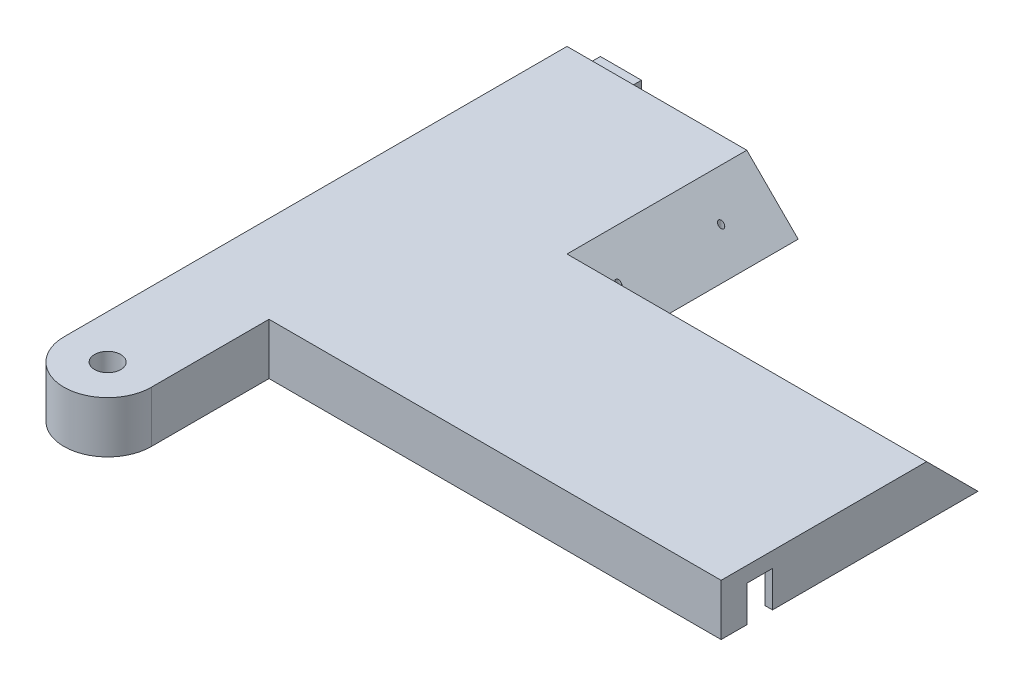
SolidWorks part; units mm, degrees
ref_plane "Front Plane" through (0, 0, 0) normal (0, 0, 1) x (1, 0, 0)
ref_plane "Top Plane" through (0, 0, 0) normal (0, 1, 0) x (1, 0, 0)
ref_plane "Right Plane" through (0, 0, 0) normal (1, 0, 0) x (0, 0, -1)
sketch "CornerrSketch1" plane through (0, 0, 0) normal (0, 1, 0) x (1, 0, 0)
  line L0 (0, 195.825) -> (90, 195.825)
  line L5 (90, 195.825) -> (90, 145.825)
  line L6 (90, 145.825) -> (210, 145.825)
  line L7 (210, 45.825) -> (210, 145.825)
  line L11 (34, 0) -> (34, 45.825)
  line L12 (34, 45.825) -> (210, 45.825)
  line L13 (0, 195.825) -> (0, 0)
  arc A0 (0, 0) -> (34, 0) centre (17, 0) ccw
  point P2 (45, 195.825)
  dimension "D3" = 34
  dimension "D4" = 90
  dimension "D2" = 100
  dimension "D1" = 45.825
  dimension "D6" = 210
  dimension "D5" = 150
extrude "CornerBoss-Extrude1" add sketch "CornerrSketch1" along normal blind 20
shell "Shell4" thickness 3 removed face at (83.5, 0, -94.7438)
sketch "PutPartialShellbackSketch1" plane through (0, 17, 0) normal (0, -1, 0) x (1, 0, 0)
  line L0 (67, -122.825) -> (67, -192.825)
  line L1 (67, -192.825) -> (87, -192.825)
  line L2 (87, -192.825) -> (87, -142.825)
  line L3 (87, -142.825) -> (207, -142.825)
  line L4 (207, -142.825) -> (207, -122.825)
  line L5 (207, -122.825) -> (67, -122.825)
  line L10 (87, -192.825) -> (3, -192.825) construction
  line L11 (207, -48.825) -> (207, -142.825) construction
  line L12 (210, -145.825) -> (90, -145.825) construction
  line L13 (90, -145.825) -> (90, -195.825) construction
  dimension "D1" = 23
  dimension "D2" = 23
extrude "PutPartialShellBackBoss-Extrude1" add sketch "PutPartialShellbackSketch1" along normal blind 17
sketch "PadSketch2" plane through (0, 17, 0) normal (0, -1, 0) x (1, 0, 0)
  circle A0 centre (17, 0) radius 12
  dimension "D1" = 24
extrude "PadBoss-Extrude2" add sketch "PadSketch2" along normal blind 10
sketch "TabHoleCutsSketch1" plane through (0, 20, 0) normal (0, 1, 0) x (1, 0, 0)
  line L4 (210, 145.825) -> (90, 145.825) construction
  line L5 (210, 45.825) -> (210, 145.825) construction
  line L6 (90, 195.825) -> (0, 195.825) construction
  line L7 (90, 145.825) -> (90, 195.825) construction
  circle A0 centre (80, 175.825) radius 1
  circle A1 centre (80, 135.825) radius 1
  circle A2 centre (135, 135.825) radius 1
  circle A3 centre (190, 135.825) radius 1
  point P16 (90, 170.825)
  dimension "D6" = 2
  dimension "D3" = 55
  dimension "D5" = 10
  dimension "D1" = 20
  dimension "D4" = 20
  dimension "D2" = 10
extrude "TabHoleCutsCut-Extrude1" cut sketch "TabHoleCutsSketch1" against normal through all
sketch "StepperShaftHoleCutSketch3" plane through (0, 7, 0) normal (0, -1, 0) x (1, 0, 0)
  circle A0 centre (17, 0) radius 5.1
  dimension "D1" = 10.2
extrude "StepperShaftHoleCut-Extrude1" cut sketch "StepperShaftHoleCutSketch3" against normal through all
sketch "ThreadedNutMountHolesSketch4" plane through (0, 7, 0) normal (0, -1, 0) x (-1, 0, 0)
  circle A8 centre (-17, 8) radius 1
  circle A9 centre (-17, -8) radius 1
  circle A10 centre (-25, 0) radius 1
  circle A11 centre (-9, 0) radius 1
  dimension "D1" = 2
  dimension "D2" = 8
  dimension "D3" = 16
  dimension "D4" = 8
  dimension "D5" = 16
extrude "ThreadedNutMountHolesCut-Extrude2" cut sketch "ThreadedNutMountHolesSketch4" against normal blind 10
sketch "BRPegHoleSketch1" plane through (210, 0, 0) normal (1, 0, 0) x (0, 0, -1)
  line L1 (55.825, 14) -> (65.825, 14)
  line L2 (55.825, 14) -> (55.825, 0)
  line L3 (55.825, 0) -> (65.825, 0)
  line L4 (65.825, 14) -> (65.825, 0)
  line L6 (45.825, 0) -> (145.825, 0) construction
  line L7 (45.825, 20) -> (45.825, 0) construction
  dimension "D2" = 10
  dimension "D3" = 14
  dimension "D1" = 10
extrude "BRPegHoleCut-Extrude1" cut sketch "BRPegHoleSketch1" against normal blind 3
sketch "TopPegSketch2" plane through (0, 0, -195.825) normal (0, 0, -1) x (-1, 0, 0)
  line L0 (0, 20) -> (0, 0) construction
  line L1 (-19.9, 13.9) -> (-10.1, 13.9)
  line L2 (-19.9, 13.9) -> (-19.9, 0)
  line L3 (-19.9, 0) -> (-10.1, 0)
  line L4 (-10.1, 13.9) -> (-10.1, 0)
  line L6 (-90, 0) -> (0, 0) construction
  dimension "D2" = 13.9
  dimension "D3" = 9.8
  dimension "D1" = 10.1
extrude "TopPegBoss-Extrude1" add sketch "TopPegSketch2" along normal blind 3
sketch "TopPegCapSketch3" plane through (0, 0, -198.825) normal (0, 0, -1) x (-1, 0, 0)
  line L1 (-22.9, 17) -> (-6.9, 17)
  line L2 (-22.9, 17) -> (-22.9, 0)
  line L3 (-22.9, 0) -> (-6.9, 0)
  line L4 (-6.9, 17) -> (-6.9, 0)
  line L5 (-19.9, 0) -> (-10.1, 0) construction
  line L7 (-19.9, 13.9) -> (-19.9, 0) construction
  dimension "D1" = 16
  dimension "D3" = 17
  dimension "D2" = 3
extrude "TopPegCapBoss-Extrude2" add sketch "TopPegCapSketch3" along normal blind 3.1
chamfer "OverLapChamfer1" distance 20 distance2 20 2 edges at (150, 20, -145.825) (90, 20, -170.825)
equation "\"RailThickness\"= .125in'Spec"
equation "\"StepperMountingHoleDistance\"= 31mm'Spec"
equation "\"StepperMountingHoleOffsetFromLeftOrRightSide\"= \"StepperMountingHoleOffsetFromItsSide\" + \"RailThickness\""
equation "\"StepperMountingHoleOffsetFromItsSide\"= 5.5mm'Spec"
equation "\"FrontBackRailLength\"= 510mm"
equation "\"DistanceBetweenLeftToRightStepperHoles\"= \"FrontBackRailLength\" - \"StepperMountingHoleOffsetFromLeftOrRightSide\" * 2 - \"StepperMountingHoleDistance\"'Equals 461.65"
equation "\"BedThickness\"= 20mm"
equation "\"BedLLongSide\"= \"BedThirdSize\" * 3'Equals 210"
equation "\"BedLShortSide\"= \"BedThirdSize\" * 2'Equals 140"
equation "\"BedLWidth\"= \"BedThirdSize\" + \"BedOverlap\"'Equals 90"
equation "\"D4@CornerrSketch1\"=\"BedLWidth\" + \"BedIncreasedByLength\"/2"
equation "\"BedIncreasedByWidth\"= 20mm"
equation "\"BedIncreasedByLength\"= 0mm"
equation "\"BedThirdSize\"= 70mm"
equation "\"BedOverlap\"= 20mm"
equation "\"BedWidth\"= \"BedInnerSquareWidth\" + \"BedLWidth\" * 2 - \"BedOverlap\" * 2 + \"BedIncreasedByWidth\"'Equals 370"
equation "\"BedInnerSquareWidth\"= \"BedThirdSize\" * 3'Equals 210"
equation "\"StandardWallThickness\"= 3mm"
equation "\"D2@BRPegHoleSketch1\"=\"BedTopPegHoleWidth\""
equation "\"D1@BRPegHoleSketch1\"=\"BedTopPegOffsetFromSide\" "
equation "\"D3@BRPegHoleSketch1\"=\"BedTopPegHoleHeight\""
equation "\"D1@BRPegHoleCut-Extrude1\" = \"StandardWallThickness\""
equation "\"D2@TopPegSketch2\"=\"BedTopPegHeight\""
equation "\"D1@TopPegBoss-Extrude1\" = \"StandardWallThickness\""
equation "\"D3@TopPegCapSketch3\"=\"BedTopPegCapHeight\""
equation "\"D1@TopPegCapSketch3\"=\"BedTopPegCapWidth\""
equation "\"D1@TopPegCapBoss-Extrude2\"=\"BedTopPegBoss\""
equation "\"D2@TopPegCapSketch3\"=\"StandardWallThickness\""
equation "\"DistanceFromBedSideToStepperHole\"= ( \"DistanceBetweenLeftToRightStepperHoles\" - \"BedWidth\" ) / 2'Equals 45.825"
equation "\"DistanceFromBedFrontToFirstLeftStepperHole\"= \"LeadScrewNutPadSize\" + 10mm'Equals 34"
equation "\"D3@CornerrSketch1\"=\"DistanceFromBedFrontToFirstLeftStepperHole\""
equation "\"LeadScrewNutPadSize\"= \"LeadScrewNutMountingHoleFlangeDiameter\" + 2mm'Equals 24"
equation "\"D1@PadSketch2\" = \"LeadScrewNutPadSize\""
equation "\"D1@StepperShaftHoleCutSketch3\"=\"LeadScrewNutInnerShaftFlangeDiameter\""
equation "\"D2@CornerrSketch1\"=\"BedLWidth\" + \"BedIncreasedByWidth\"/2"
equation "\"D6@CornerrSketch1\"=\"BedLLongSide\""
equation "\"D1@TopPegSketch2\"=\"BedTopPegOffsetFromSide\" + .1mm"
equation "\"D1@CornerrSketch1\"=\"DistanceFromBedSideToStepperHole\""
equation "\"D5@CornerrSketch1\"=\"BedLShortSide\" + \"BedIncreasedByWidth\"/2"
equation "\"LeadScrewNutInnerShaftFlangeDiameter\"= 10.2mm'Spec"
equation "\"LeadScrewNutMountHoleDiameter\"= 2mm'Spec is 4.1 but smaller for tapping"
equation "\"LeadScrewNutMountingHoleFlangeDiameter\"= 22mm'Spec"
equation "\"LeadScrewNutMountingHoleDistance\"= 16mm'Spec"
equation "\"D1@ThreadedNutMountHolesSketch4\"=\"LeadScrewNutMountHoleDiameter\""
equation "\"D2@ThreadedNutMountHolesSketch4\"=\"LeadScrewNutMountingHoleDistance\"/2"
equation "\"D3@ThreadedNutMountHolesSketch4\"=\"LeadScrewNutMountingHoleDistance\""
equation "\"D4@ThreadedNutMountHolesSketch4\"=\"LeadScrewNutMountingHoleDistance\"/2"
equation "\"D5@ThreadedNutMountHolesSketch4\"=\"LeadScrewNutMountingHoleDistance\""
equation "\"LeadScrewNutPadDepth\"= \"BedThickness\" / 2'Equals 10"
equation "\"D1@PadBoss-Extrude2\"=\"LeadScrewNutPadDepth\""
equation "\"D1@ThreadedNutMountHolesCut-Extrude2\"= \"LeadScrewNutPadDepth\""
equation "\"BedTopPegHoleWidth\"= 10mm"
equation "\"BedTopPegHoleHeight\"= \"BedThickness\"- \"StandardWallThickness\"* 2' Equals 14"
equation "\"BedTopPegWidth\"= \"BedTopPegHoleWidth\"- .1mm* 2'For easier assembly"
equation "\"BedTopPegHeight\"= \"BedTopPegHoleHeight\"- .1mm'For easier assembly"
equation "\"BedTopPegOffsetFromSide\"= 10mm"
equation "\"BedTopPegBoss\"= \"StandardWallThickness\"+ .1mm'For easier assembly"
equation "\"BedTopPegCapHeight\"= \"BedThickness\"- \"StandardWallThickness\"'Equals 17"
equation "\"BedTopPegCapWidth\"= \"BedThickness\"/2 + \"StandardWallThickness\"*2'Equals 16"
equation "\"D3@TopPegSketch2\"=\"BedTopPegWidth\""
equation "\"D5@TabHoleCutsSketch1\"=\"BedOverlap\"/2"
equation "\"D1@TabHoleCutsSketch1\"=\"BedOverlap\""
equation "\"D4@TabHoleCutsSketch1\"=\"BedOverlap\""
equation "\"D2@TabHoleCutsSketch1\"=\"BedOverlap\"/2"
equation "\"D1@PutPartialShellbackSketch1\"=\"BedOverlap\" + \"StandardWallThickness\""
equation "\"D2@PutPartialShellbackSketch1\"=\"BedOverlap\" + \"StandardWallThickness\""
equation "\"D3@OverLapChamfer1\"=\"BedOverlap\""
equation "\"D1@OverLapChamfer1\"=\"BedThickness\""
equation "\"D1@PutPartialShellBackBoss-Extrude1\"=\"BedThickness\" - \"StandardWallThickness\""
